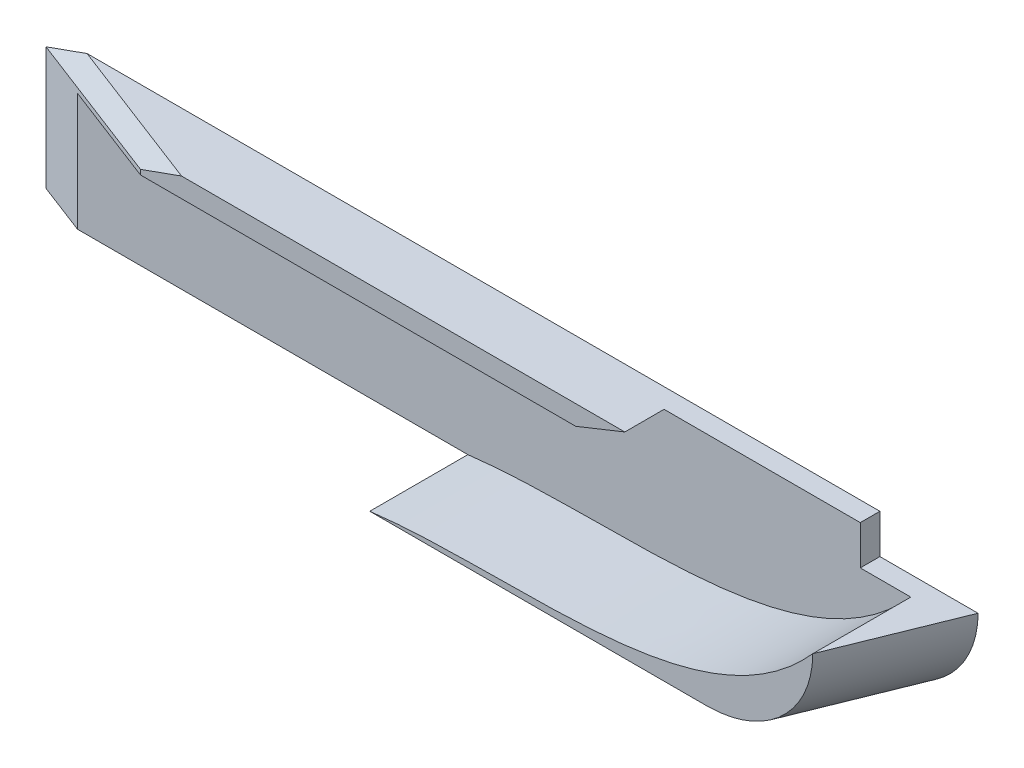
SolidWorks part; units mm, degrees
ref_plane "Płaszczyzna przednia" through (0, 0, 0) normal (0, 0, 1) x (1, 0, 0)
ref_plane "Płaszczyzna górna" through (0, 0, 0) normal (0, 1, 0) x (1, 0, 0)
ref_plane "Płaszczyzna prawa" through (0, 0, 0) normal (1, 0, 0) x (0, 0, -1)
sketch "Sketch1" plane through (0, 0, 0) normal (0, 0, 1) x (1, 0, 0)
  line L1 (-52.0588, 11.9069) -> (32.9412, 11.9069)
  line L2 (-52.0588, 11.9069) -> (-52.0588, -2.0931)
  line L3 (-52.0588, -2.0931) -> (32.9412, -2.0931)
  line L4 (32.9412, 11.9069) -> (32.9412, -2.0931)
  dimension "D1" = 14
  dimension "D2" = 85
extrude "Boss-Extrude1" add sketch "Sketch1" along normal blind 2
sketch "Sketch2" plane through (0, 0, 0) normal (0, 0, 1) x (1, 0, 0)
  line L1 (-52.0588, 9.9069) -> (32.9412, 9.9069)
  line L2 (-52.0588, 9.9069) -> (-52.0588, 11.9069)
  line L3 (-52.0588, 11.9069) -> (32.9412, 11.9069)
  line L4 (32.9412, 9.9069) -> (32.9412, 11.9069)
  dimension "D1" = 2
extrude "Boss-Extrude2" add sketch "Sketch2" along normal blind 6
sketch "Sketch3" plane through (0, 0, 0) normal (0, 0, -1) x (-1, 0, 0)
  line L1 (-42.9412, 7.9069) -> (-42.9412, -2.0931)
  line L3 (-32.9412, -2.0931) -> (-32.9412, 7.9069)
  line L4 (-32.9412, -2.0931) -> (-32.9412, 11.9069) construction
  line L5 (-32.9412, 7.9069) -> (-42.9412, 7.9069)
  line L6 (-42.9412, -2.0931) -> (-32.9412, -2.0931)
  dimension "D1" = 10
  dimension "D2" = 10
extrude "Boss-Extrude3" add sketch "Sketch3" against normal blind 2
sketch "Sketch4" plane through (0, 0, 6) normal (0, 0, 1) x (1, 0, 0)
  line L0 (7.9412, 9.9069) -> (12.9412, 11.9069)
  line L1 (32.9412, 9.9069) -> (-52.0588, 9.9069) construction
  line L2 (32.9412, 11.9069) -> (-52.0588, 11.9069) construction
  line L3 (12.9412, 11.9069) -> (32.9412, 11.9069)
  line L4 (32.9412, 11.9069) -> (32.9412, 9.9069)
  line L5 (32.9412, 9.9069) -> (7.9412, 9.9069)
  dimension "D1" = 20
  dimension "D2" = 25
extrude "Cut-Extrude1" cut sketch "Sketch4" against normal blind 4
sketch "Sketch5" plane through (0, 11.9069, 0) normal (0, 1, 0) x (1, 0, 0)
  line L0 (-52.0588, 0) -> (-36.4283, -6)
  line L1 (12.9412, -6) -> (-52.0588, -6) construction
  line L2 (-36.4283, -6) -> (-52.0588, -6)
  line L3 (-52.0588, -6) -> (-52.0588, 0)
  dimension "D1" = 21
extrude "Cut-Extrude2" cut sketch "Sketch5" against normal blind 20
chamfer "Chamfer1" distance 1.5 angle 45 1 edges at (-44.2436, 11.9069, 3)
sketch "Sketch6" plane through (42.9412, 0, 0) normal (1, 0, 0) x (0, 0, -1)
  line L1 (-2, -2.0931) -> (-12, -2.0931)
  line L2 (-2, -2.0931) -> (-2, 7.9069)
  line L3 (-2, 7.9069) -> (-12, 7.9069)
  line L4 (-12, -2.0931) -> (-12, 7.9069)
  dimension "D1" = 10
  dimension "D2" = 10
extrude "Boss-Extrude4" add sketch "Sketch6" against normal blind 50
sketch "Sketch7" plane through (0, -2.0931, 0) normal (0, -1, 0) x (1, 0, 0)
  line L0 (42.9412, 0) -> (38.0929, 12)
  line L1 (-7.0588, 12) -> (42.9412, 12) construction
  line L2 (38.0929, 12) -> (42.9412, 12)
  line L3 (42.9412, 12) -> (42.9412, 0)
  line L4 (-52.0588, 0) -> (42.9412, 0) construction
  dimension "D1" = 68
extrude "Cut-Extrude3" cut sketch "Sketch7" against normal blind 50
fillet "Fillet1" radius 10 1 edges at (40.517, -2.0931, 6)
sketch "Sketch8" plane through (0, 0, 12) normal (0, 0, 1) x (1, 0, 0)
  line L0 (-7.0588, -2.0931) -> (27.3075, -2.0931) construction
  line L1 (-7.0588, -2.0931) -> (-7.0588, 7.9069) construction
  line L2 (-7.0588, -2.0931) -> (-7.0588, 7.9069)
  line L3 (-7.0588, 7.9069) -> (38.0929, 7.9069)
  spline S0 degree 3 poles (-7.0588, -2.0931) (8.2539, -0.1959) (26.8793, -4.674) (38.0929, 7.9069) knots 0 0 0 0 1 1 1 1
  dimension "D1" = 0.5
  dimension "D2" = 7
  dimension "D3" = 38
  dimension "D4" = 4.5
extrude "Cut-Extrude4" cut sketch "Sketch8" against normal blind 10
